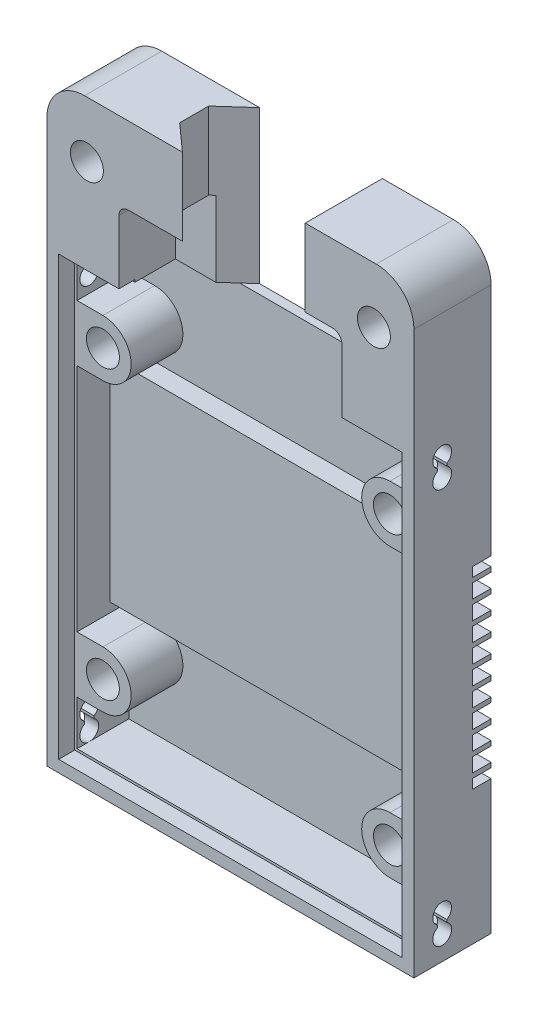
SolidWorks part; units mm, degrees
ref_plane "Front Plane" through (0, 0, 0) normal (0, 0, 1) x (1, 0, 0)
ref_plane "Top Plane" through (0, 0, 0) normal (0, 1, 0) x (1, 0, 0)
ref_plane "Right Plane" through (0, 0, 0) normal (1, 0, 0) x (0, 0, -1)
sketch "Sketch1" plane through (0, 0, 0) normal (0, 0, 1) x (1, 0, 0)
  line L0 (15.25, -20.35) -> (18, -20.35)
  line L1 (-19.5, -32.6) -> (19.5, -32.6)
  line L2 (-19.5, -32.6) -> (-19.5, 31.1)
  line L3 (-19.5, 31.1) -> (19.5, 31.1)
  line L4 (19.5, -32.6) -> (19.5, 31.1)
  line L5 (-15.25, -20.35) -> (-18, -20.35)
  line L6 (15.25, -26.35) -> (18, -26.35)
  line L7 (15.5, 31.1) -> (-15.5, 31.1) construction
  line L8 (-18, -31.1) -> (-18, 29.6)
  line L9 (-18, 29.6) -> (18, 29.6)
  line L10 (18, -31.1) -> (18, 29.6)
  line L11 (-18, -31.1) -> (18, -31.1)
  line L12 (-18, 14.9) -> (18, 14.9)
  line L13 (7.85, 14.9) -> (-4.95, 14.9) construction
  line L14 (-15.25, 4.15) -> (-18, 4.15)
  line L15 (-15.25, 10.15) -> (-18, 10.15)
  line L16 (15.25, 10.15) -> (18, 10.15)
  line L17 (15.25, 4.15) -> (18, 4.15)
  line L18 (-15.25, -26.35) -> (-18, -26.35)
  arc A0 (19.5, 27.1) -> (15.5, 31.1) centre (15.5, 27.1) ccw construction
  arc A1 (-15.5, 31.1) -> (-19.5, 27.1) centre (-15.5, 27.1) ccw construction
  arc A2 (19.5, 27.1) -> (15.5, 31.1) centre (15.5, 27.1) ccw
  arc A3 (-15.5, 31.1) -> (-19.5, 27.1) centre (-15.5, 27.1) ccw
  arc A4 (-15.5, 29.6) -> (-18, 27.1) centre (-15.5, 27.1) ccw
  arc A5 (18, 27.1) -> (15.5, 29.6) centre (15.5, 27.1) ccw
  circle A6 centre (-15.25, -23.35) radius 1.75
  circle A7 centre (15.25, -23.35) radius 1.75
  circle A8 centre (-15.25, 7.15) radius 1.75
  circle A9 centre (15.25, 7.15) radius 1.75
  circle A10 centre (15.25, 25.15) radius 1.75
  circle A11 centre (-15.25, 25.15) radius 1.75
  circle A12 centre (-15.25, -23.35) radius 3
  circle A13 centre (15.25, -23.35) radius 3
  circle A14 centre (15.25, 7.15) radius 3
  circle A15 centre (-15.25, 7.15) radius 3
  dimension "D2" = 1.5
  dimension "D4" = 6
  dimension "D3" = 3.5
  dimension "D1" = 1.5
extrude "Base shape" add sketch "Sketch1" along normal up to surface (8.2 mm away) contours L10 A5 L9 A4 L8 L12 A11 A10 | L3 A3 L2 L1 L4 A2 A15 L8 L9 L10 A14 A13 L11 A12 | A4 L9 L8 | A5 L10 L9 | A15 L15 L8 | A15 L8 A8 | A15 L8 L14 | L8 A15 | A14 L17 L10 | L10 A14 A9 | L10 A14 | A14 L10 L16 | A13 L6 L10 | L10 A13 A7 | L10 A13 | A13 L10 L0 | A12 L8 L18 | A12 L8 A6 | L8 A12 | A12 L5 L8 region at (16.8481, -20.9099, 0) region at (17.3601, -20.8437, 0) region at (17.3601, -25.8563, 0) region at (18.1004, -23.35, 0) region at (17.3601, 4.6437, 0) region at (16.8481, 4.7099, 0) region at (18.1004, 7.15, 0) region at (17.3601, 9.6563, 0) region at (-17.3601, -25.8563, 0) region at (0, 22.1041, 0) region at (-18.1004, -23.35, 0) region at (-17.9169, -23.35, 0) region at (17.4416, 29.0416, 0) region at (-17.3601, -20.8437, 0) region at (-17.3601, 9.6563, 0) region at (-17.4416, 29.0416, 0) region at (-16.8481, 9.5901, 0) region at (-18.1004, 7.15, 0) region at (-17.3601, 4.6437, 0) region at (-18.7531, -2.75, 0)
sketch "Sketch3" plane through (19.5, 0, 0) normal (1, 0, 0) x (0, 0, -1)
  line L1 (0, -18.35) -> (-2, -18.35)
  line L2 (0, -18.35) -> (0, 2.15)
  line L3 (0, 2.15) -> (-2, 2.15)
  line L4 (-2, -18.35) -> (-2, 2.15)
  line L5 (0, -18.35) -> (2, -18.35) construction
  line L6 (0, 2.15) -> (2, 2.15) construction
  line L7 (0, -32.6) -> (0, 27.1) construction
  dimension "D1" = 2
extrude "Strap cut" cut sketch "Sketch3" against normal through all
sketch "Sketch4" plane through (0, 31.1, 0) normal (0, 1, 0) x (1, 0, 0)
  line L2 (7.95, 0) -> (-5.0998, 0)
  line L4 (-15.5, 0) -> (15.5, 0) construction
  line L5 (-15.5, -8.2) -> (15.5, -8.2) construction
  line L6 (7.95, -8.2) -> (-5.0998, -8.2)
  line L12 (7.95, -8.3) -> (7.95, 0.1)
  line L13 (7.95, 0.1) -> (-4.9883, 0.1)
  line L14 (-4.9883, 0.1) -> (-7.95, -2.5553)
  line L15 (-7.95, -2.5553) -> (-7.95, -5.6447)
  line L16 (-7.95, -5.6447) -> (-4.9883, -8.3)
  line L17 (-4.9883, -8.3) -> (7.95, -8.3)
  line L18 (7.95, -8.3) -> (7.95, 0.1)
  line L19 (7.95, 0.1) -> (-4.9883, 0.1)
  line L20 (-4.9883, 0.1) -> (-7.95, -2.5553)
  line L21 (-7.95, -2.5553) -> (-7.95, -5.6447)
  line L22 (-7.95, -5.6447) -> (-4.9883, -8.3)
  line L23 (-4.9883, -8.3) -> (7.95, -8.3)
  dimension "D1" = 0.1
extrude "XT60 cut" cut sketch "Sketch4" against normal up to next contours L21 L22 L18 L20 region at (0.4142, 31.1, 4.1)
sketch "Sketch5" plane through (19.5, 0, 0) normal (1, 0, 0) x (0, 0, -1)
  line L1 (-8.2, -32.6) -> (-8.2, 27.1) construction
  line L2 (-6.2, -31.1) -> (-4.2, -31.1)
  line L3 (-6.2, -31.1) -> (-6.2, -27.1)
  line L4 (-6.2, -27.1) -> (-4.2, -27.1)
  line L5 (-4.2, -31.1) -> (-4.2, -27.1)
  line L6 (-8.2, -31.1) -> (0, -31.1) construction
  line L7 (-8.2, 14.9) -> (0, 14.9) construction
  line L8 (-6.2, 14.9) -> (-4.2, 14.9)
  line L9 (-6.2, 14.9) -> (-6.2, 10.9)
  line L10 (-6.2, 10.9) -> (-4.2, 10.9)
  line L11 (-4.2, 14.9) -> (-4.2, 10.9)
  line L14 (-5.2, -27.1) -> (-5.2, -31.1) construction
  line L15 (-5.2, 14.9) -> (-5.2, 10.9) construction
  line L16 (-5.7, -31.1) -> (-4.7, -31.1)
  line L17 (-5.7, -31.1) -> (-5.7, -27.1)
  line L18 (-5.7, -27.1) -> (-4.7, -27.1)
  line L19 (-4.7, -31.1) -> (-4.7, -27.1)
  line L20 (-5.7, -31.1) -> (-4.7, -27.1) construction
  line L21 (-5.7, -27.1) -> (-4.7, -31.1) construction
  line L23 (-5.7, 10.9) -> (-4.7, 10.9)
  line L24 (-5.7, 10.9) -> (-5.7, 14.9)
  line L25 (-5.7, 14.9) -> (-4.7, 14.9)
  line L26 (-4.7, 10.9) -> (-4.7, 14.9)
  line L27 (-5.7, 10.9) -> (-4.7, 14.9) construction
  line L28 (-5.7, 14.9) -> (-4.7, 10.9) construction
  circle A0 centre (-5.2, -28.1) radius 1
  circle A1 centre (-5.2, -30.1) radius 1
  circle A2 centre (-5.2, 13.9) radius 1
  circle A3 centre (-5.2, 11.9) radius 1
  point P20 (-5.2, -29.1)
  point P31 (-5.2, 12.9)
  dimension "D3" = 4
  dimension "D1" = 2
  dimension "D2" = 2
  dimension "D4" = 1
extrude "Power wires cut" cut sketch "Sketch5" against normal through all contours A2 L26 | L26 A2 L24 | L24 A2 | A3 A2 L24 | A3 L26 A2 | L26 A3 L24 | L24 A3 | A3 L26 | A0 L19 | L19 A0 L17 | L17 A0 | L19 A1 L17 | L17 A1 | A1 L19 | A1 L19 A0 | A1 A0 L17 region at (19.5, -30.1, 5.905) region at (19.5, -30.1, 5.2) region at (19.5, -28.1, 5.905) region at (19.5, -29.1, 5.5767) region at (19.5, -30.1, 4.495) region at (19.5, -28.1, 5.2) region at (19.5, -29.1, 4.8233) region at (19.5, -28.1, 4.495) region at (19.5, 13.9, 5.905) region at (19.5, 13.9, 5.2) region at (19.5, 11.9, 5.905) region at (19.5, 12.9, 5.5767) region at (19.5, 13.9, 4.495) region at (19.5, 11.9, 5.2) region at (19.5, 12.9, 4.8233) region at (19.5, 11.9, 4.495)
sketch "Sketch6" plane through (0, 0, 8.2) normal (0, 0, 1) x (1, 0, 0)
  line L0 (-7.85, 15.9) -> (-7.85, 21.9) construction
  line L1 (-8.85, 22.9) -> (-10.85, 22.9) construction
  line L2 (-11.85, 15.9) -> (-11.85, 21.9) construction
  line L3 (-8.85, 14.9) -> (-10.85, 14.9) construction
  line L4 (-7.85, 15.9) -> (-7.85, 21.9)
  line L5 (-8.85, 22.9) -> (-10.85, 22.9)
  line L6 (-11.85, 15.9) -> (-11.85, 21.9)
  line L7 (-8.85, 14.9) -> (-10.85, 14.9)
  line L8 (7.85, 15.9) -> (7.85, 21.9) construction
  line L9 (8.85, 22.9) -> (10.85, 22.9) construction
  line L10 (11.85, 15.9) -> (11.85, 21.9) construction
  line L11 (8.85, 14.9) -> (10.85, 14.9) construction
  line L12 (7.85, 15.9) -> (7.85, 21.9)
  line L13 (8.85, 22.9) -> (10.85, 22.9)
  line L14 (11.85, 15.9) -> (11.85, 21.9)
  line L15 (8.85, 14.9) -> (10.85, 14.9)
  line L17 (-11.85, 15.9) -> (-7.85, 15.9)
  line L18 (-11.85, 15.9) -> (-11.85, 14.9)
  line L19 (-11.85, 14.9) -> (-7.85, 14.9)
  line L20 (-7.85, 15.9) -> (-7.85, 14.9)
  line L22 (11.85, 15.9) -> (7.85, 15.9)
  line L23 (11.85, 15.9) -> (11.85, 14.9)
  line L24 (11.85, 14.9) -> (7.85, 14.9)
  line L25 (7.85, 15.9) -> (7.85, 14.9)
  line L26 (-18, 14.9) -> (-5.0998, 14.9) construction
  line L27 (11.85, 21.9) -> (7.85, 21.9)
  line L28 (11.85, 21.9) -> (11.85, 22.9)
  line L29 (11.85, 22.9) -> (7.85, 22.9)
  line L30 (7.85, 21.9) -> (7.85, 22.9)
  line L31 (-8.85, 22.9) -> (7.95, 22.9)
  line L32 (-8.85, 22.9) -> (-8.85, 14.9)
  line L33 (-8.85, 14.9) -> (7.95, 14.9)
  line L34 (7.95, 22.9) -> (7.95, 14.9)
  line L35 (7.95, 14.9) -> (18, 14.9) construction
  line L36 (7.95, 14.9) -> (7.95, 31.1) construction
  arc A0 (-8.85, 14.9) -> (-7.85, 15.9) centre (-8.85, 15.9) ccw construction
  arc A1 (-7.85, 21.9) -> (-8.85, 22.9) centre (-8.85, 21.9) ccw construction
  arc A2 (-10.85, 22.9) -> (-11.85, 21.9) centre (-10.85, 21.9) ccw construction
  arc A3 (-11.85, 15.9) -> (-10.85, 14.9) centre (-10.85, 15.9) ccw construction
  arc A4 (-8.85, 14.9) -> (-7.85, 15.9) centre (-8.85, 15.9) ccw
  arc A5 (-7.85, 21.9) -> (-8.85, 22.9) centre (-8.85, 21.9) ccw
  arc A6 (-10.85, 22.9) -> (-11.85, 21.9) centre (-10.85, 21.9) ccw
  arc A7 (-11.85, 15.9) -> (-10.85, 14.9) centre (-10.85, 15.9) ccw
  arc A8 (8.85, 22.9) -> (7.85, 21.9) centre (8.85, 21.9) ccw construction
  arc A9 (11.85, 21.9) -> (10.85, 22.9) centre (10.85, 21.9) ccw construction
  arc A10 (10.85, 14.9) -> (11.85, 15.9) centre (10.85, 15.9) ccw construction
  arc A11 (7.85, 15.9) -> (8.85, 14.9) centre (8.85, 15.9) ccw construction
  arc A12 (8.85, 22.9) -> (7.85, 21.9) centre (8.85, 21.9) ccw
  arc A13 (11.85, 21.9) -> (10.85, 22.9) centre (10.85, 21.9) ccw
  arc A14 (10.85, 14.9) -> (11.85, 15.9) centre (10.85, 15.9) ccw
  arc A15 (7.85, 15.9) -> (8.85, 14.9) centre (8.85, 15.9) ccw
  line M1 (7.95, 31.1) -> (7.95, 14.9)
  line M15 (-5.0998, 14.9) -> (-5.0998, 31.1)
extrude "IO wires cut" cut sketch "Sketch6" against normal blind 6 contours L33 L25 L12 L30 L31 M15 | A5 L4 L20 L31 M15 | L4 A5 L32 L17 | L5 A6 L6 L17 L32 | A7 L18 | L17 A7 L32 | L32 A4 L17 | A4 L20 | A12 L29 L30 M1 | L27 L12 L22 M1 | L22 A15 M1 | A15 L25 L24 L34 | A15 L34 | A15 A14 L22 M1 | A14 L23 | L14 L27 L22 M1 | L27 A13 L13 A12 L34 | A12 L29 M1 region at (-8.3587, 19.2964, 8.2) region at (-8.4256, 15.4756, 8.2) region at (-6.4903, 18.9365, 8.2) region at (-8.0734, 15.1234, 8.2) region at (-10.2516, 15.4213, 8.2) region at (-10.3368, 19.3662, 8.2) region at (-11.6266, 15.1234, 8.2) region at (1.3751, 18.9, 8.2) region at (7.8959, 15.2606, 8.2) region at (7.8959, 22.5394, 8.2) region at (8.1604, 15.056, 8.2) region at (7.9, 18.9, 8.2) region at (7.9098, 15.7354, 8.2) region at (8.1604, 22.744, 8.2) region at (9.8661, 15.4307, 8.2) region at (9.9, 18.9, 8.2) region at (9.8661, 22.3693, 8.2) region at (11.6266, 15.1234, 8.2)
sketch "Sketch7" plane through (-18, 0, 0) normal (1, 0, 0) x (0, 0, -1)
  line L6 (0, -18.35) -> (0, -20.35)
  line L7 (-2, -18.35) -> (0, -18.35)
  line L8 (-2, 2.15) -> (-2, -18.35)
  line L9 (0, 2.15) -> (-2, 2.15)
  line L12 (0, 3.15) -> (-3, 3.15)
  line L13 (-3, 3.15) -> (-3, -19.35)
  line L14 (-3, -19.35) -> (-1, -19.35)
  line L15 (-1, -19.35) -> (-1, -20.35)
  line L16 (-1, -20.35) -> (0, -20.35)
  line L17 (0, 3.15) -> (-1, 3.15)
  line L19 (0, -31.1) -> (-1, -31.1)
  line L22 (0, -31.1) -> (0, -20.35)
  line L23 (0, -20.35) -> (-1, -20.35)
  line L24 (-1, -31.1) -> (-1, -20.35)
  line L25 (0, 3.15) -> (0, 14.9)
  line L26 (0, 14.9) -> (-1, 14.9)
  line L27 (-1, 3.15) -> (-1, 14.9)
  line L28 (-5.2, 14.9) -> (0, 14.9) construction
  line L31 (0, -20.35) -> (0, -18.35) construction
  line L32 (0, 2.15) -> (-2, 2.15) construction
  line M48 (0, -20.35) -> (0, -18.35)
  line M49 (0, -18.35) -> (-2, -18.35)
  line M50 (-2, -18.35) -> (-2, 2.15)
  line M51 (-2, 2.15) -> (0, 2.15)
  line M52 (0, 2.15) -> (0, 4.15)
  line M53 (0, 4.15) -> (-8.2, 4.15)
  line M55 (-8.2, -20.35) -> (0, -20.35)
  dimension "D1" = 1
extrude "Bottom" add sketch "Sketch7" along normal up to surface (36 mm away) contours L27 L25 L26 M53 | L27 L12 M52 M53 | L14 L15 L12 L13 M55 M48 M49 M50 M51 M52 | L24 L19 L22 M55 region at (-18, -8.5273, 2.2091) region at (-18, -25.725, 0.5) region at (-18, 3.65, 0.5) region at (-18, 9.525, 0.5) up to face at (18, -8.1, 2.55)
sketch "Sketch9" plane through (0, 0, 0) normal (0, 0, -1) x (-1, 0, 0)
  circle A0 centre (-15.25, -23.35) radius 1.75 construction
  circle A1 centre (-15.25, 7.15) radius 1.75 construction
  circle A2 centre (15.25, 7.15) radius 1.75 construction
  circle A3 centre (15.25, -23.35) radius 1.75 construction
  circle A4 centre (-15.25, -23.35) radius 1.75
  circle A5 centre (-15.25, 7.15) radius 1.75
  circle A6 centre (15.25, 7.15) radius 1.75
  circle A7 centre (15.25, -23.35) radius 1.75
extrude "Bottom holes" cut sketch "Sketch9" against normal up to next
sketch "Sketch8" plane through (0, 0, 8.2) normal (0, 0, 1) x (1, 0, 0)
  line L0 (-6.2152, 14.9) -> (-18, 14.9) construction
  line L1 (-18.25, 15.15) -> (18.25, 15.15)
  line L2 (-18.25, 15.15) -> (-18.25, -31.35)
  line L3 (-18.25, -31.35) -> (18.25, -31.35)
  line L4 (18.25, 15.15) -> (18.25, -31.35)
  line L5 (-18, 14.9) -> (-18.25, 14.9) construction
  line L6 (-18, 14.9) -> (-18, 15.15) construction
  line L7 (18, 14.9) -> (18.25, 14.9) construction
  line L8 (-18, -31.1) -> (-18, -31.35) construction
  dimension "D1" = 0.25
extrude "PCB cut" cut sketch "Sketch8" against normal blind 1.7
sketch "Sketch10" plane through (0, 0, 2) normal (0, 0, -1) x (-1, 0, 0)
  line L0 (0, 2.15) -> (0, -18.35) construction
  line L1 (19.5, 2.15) -> (-19.5, 2.15) construction
  line L2 (19.5, -18.35) -> (-19.5, -18.35) construction
  line L3 (19.5, 2.15) -> (19.5, -18.35) construction
  line L4 (-19.5, 1.15) -> (19.5, 1.15)
  line L5 (-19.5, 1.15) -> (-19.5, 0.65)
  line L6 (-19.5, 0.65) -> (19.5, 0.65)
  line L7 (19.5, 1.15) -> (19.5, 0.65)
  line L8 (-19.5, 1.15) -> (19.5, 0.65) construction
  line L9 (-19.5, 0.65) -> (19.5, 1.15) construction
  line L10 (-19.5, 2.15) -> (19.5, 2.15) construction
  line L11 (-19.5, -1.35) -> (19.5, -1.35)
  line L12 (19.5, -0.85) -> (19.5, -1.35)
  line L13 (-19.5, -0.85) -> (19.5, -0.85)
  line L14 (-19.5, -0.85) -> (-19.5, -1.35)
  line L15 (-19.5, -3.35) -> (19.5, -3.35)
  line L16 (19.5, -2.85) -> (19.5, -3.35)
  line L17 (-19.5, -2.85) -> (19.5, -2.85)
  line L18 (-19.5, -2.85) -> (-19.5, -3.35)
  line L19 (-19.5, -5.35) -> (19.5, -5.35)
  line L20 (19.5, -4.85) -> (19.5, -5.35)
  line L21 (-19.5, -4.85) -> (19.5, -4.85)
  line L22 (-19.5, -4.85) -> (-19.5, -5.35)
  line L23 (-19.5, -7.35) -> (19.5, -7.35)
  line L24 (19.5, -6.85) -> (19.5, -7.35)
  line L25 (-19.5, -6.85) -> (19.5, -6.85)
  line L26 (-19.5, -6.85) -> (-19.5, -7.35)
  line L27 (-19.5, -9.35) -> (19.5, -9.35)
  line L28 (19.5, -8.85) -> (19.5, -9.35)
  line L29 (-19.5, -8.85) -> (19.5, -8.85)
  line L30 (-19.5, -8.85) -> (-19.5, -9.35)
  line L31 (-19.5, -11.35) -> (19.5, -11.35)
  line L32 (19.5, -10.85) -> (19.5, -11.35)
  line L33 (-19.5, -10.85) -> (19.5, -10.85)
  line L34 (-19.5, -10.85) -> (-19.5, -11.35)
  line L35 (-19.5, -13.35) -> (19.5, -13.35)
  line L36 (19.5, -12.85) -> (19.5, -13.35)
  line L37 (-19.5, -12.85) -> (19.5, -12.85)
  line L38 (-19.5, -12.85) -> (-19.5, -13.35)
  line L39 (-19.5, -15.35) -> (19.5, -15.35)
  line L40 (19.5, -14.85) -> (19.5, -15.35)
  line L41 (-19.5, -14.85) -> (19.5, -14.85)
  line L42 (-19.5, -14.85) -> (-19.5, -15.35)
  line L43 (-19.5, -17.35) -> (19.5, -17.35)
  line L44 (19.5, -16.85) -> (19.5, -17.35)
  line L45 (-19.5, -16.85) -> (19.5, -16.85)
  line L46 (-19.5, -16.85) -> (-19.5, -17.35)
  point P6 (0, 0.9)
  dimension "D1" = 1
  dimension "D2" = 0.5
  dimension "D4" = 2
  dimension "D3" = 10
extrude "Boss-Extrude1" add sketch "Sketch10" along normal up to surface (2 mm away) up to face at (13.5, 7.15, 0)
